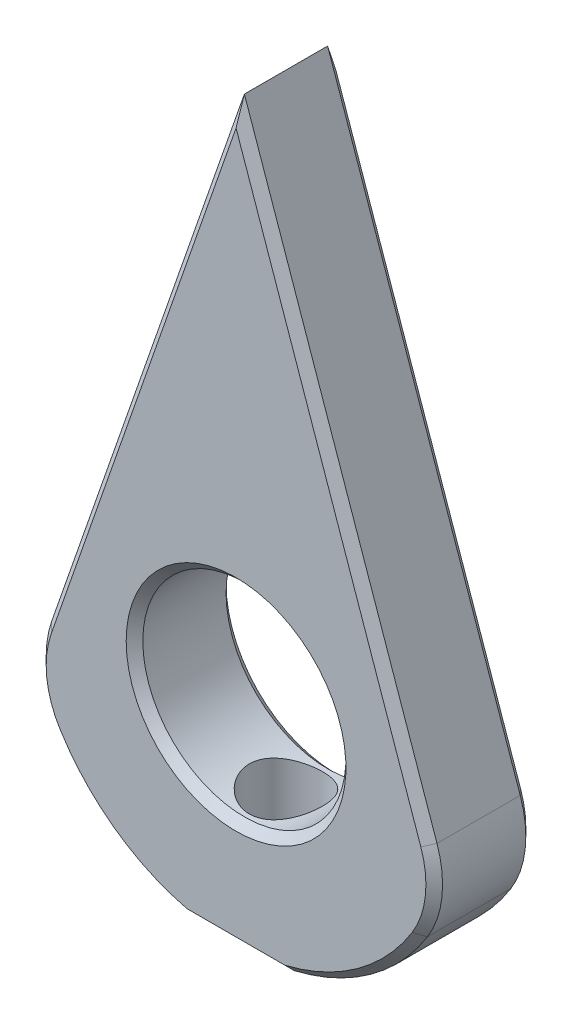
SolidWorks part; units mm, degrees
ref_plane "Front" through (0, 0, 0) normal (0, 0, 1) x (1, 0, 0)
ref_plane "Top" through (0, 0, 0) normal (0, 1, 0) x (1, 0, 0)
ref_plane "Right" through (0, 0, 0) normal (1, 0, 0) x (0, 0, -1)
sketch "Skizze1" plane through (0, 0, 0) normal (0, 0, 1) x (1, 0, 0)
  line L0 (0, 0) -> (0, 20.0957) construction
  line L3 (0, 0) -> (0, -13.0268) construction
  line L4 (-3, -12.6) -> (3, -12.6)
  line L5 (12.3451, -3.9191) -> (0, 31.5)
  line L6 (-12.3451, -3.9191) -> (0, 31.5)
  circle A0 centre (0, 0) radius 6.1
  arc A2 (3, -12.6) -> (12.3451, -3.9191) centre (0, 0) ccw
  arc A3 (-3, -12.6) -> (-12.3451, -3.9191) centre (0, 0) cw
  point P8 (0, -6.1)
  point P9 (0, -12.6)
  dimension "D1" = 12.2
  dimension "D2" = 6.5
  dimension "D3" = 6
  dimension "D4" = 31.5
extrude "Aufsatz-Linear austragen1" add sketch "Skizze1" along normal blind 6
sketch "Skizze2" plane through (0, -12.6, 0) normal (0, -1, 0) x (1, 0, 0)
  line L0 (0, 0) -> (0, 6) construction
  line L1 (-3, 0) -> (3, 0) construction
  line L2 (-3, 6) -> (3, 6) construction
  circle A0 centre (0, 3) radius 2.2
  dimension "D1" = 4.4
extrude "Schnitt-Linear austragen1" cut sketch "Skizze2" against normal up to next
fillet "Verrundung1" radius 6 2 edges at (12.3451, -3.9191, 3) (-12.3451, -3.9191, 3)
chamfer "Fase1" distance 0.5 angle 45 16 edges at (6.1, 0, 0) (0, -12.6, 0) (7.5697, -10.51, 0) (5.785, 14.9022, 0) (-5.785, 14.9022, 0) (-7.5697, -10.51, 0) (6.1, 0, 6) (-5.785, 14.9022, 6) (5.785, 14.9022, 6) (7.5697, -10.51, 6) (0, -12.6, 6) (-7.5697, -10.51, 6) (-11.8679, -4.3314, 0) (11.8679, -4.3314, 0) (-11.8679, -4.3314, 6) (11.8679, -4.3314, 6)
